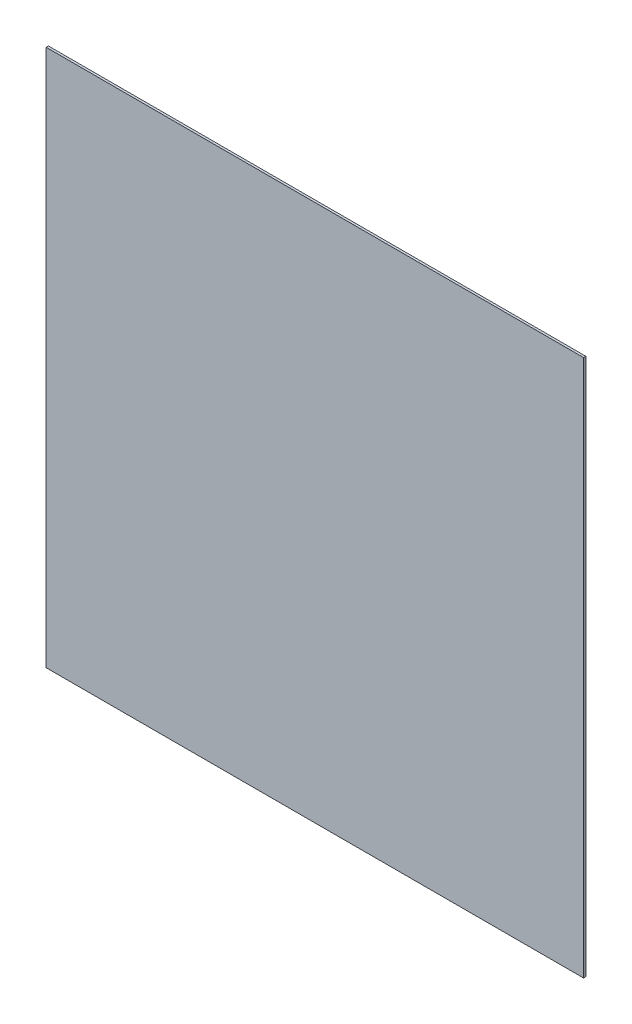
SolidWorks part; units mm, degrees
material "Mahogany"
ref_plane "Front Plane" through (0, 0, 0) normal (0, 0, 1) x (1, 0, 0)
ref_plane "Top Plane" through (0, 0, 0) normal (0, 1, 0) x (1, 0, 0)
ref_plane "Right Plane" through (0, 0, 0) normal (1, 0, 0) x (0, 0, -1)
sketch "Sketch1" plane through (0, 0, 0) normal (0, 0, 1) x (1, 0, 0)
  line L1 (-375, 375) -> (375, 375)
  line L2 (-375, 375) -> (-375, -375)
  line L3 (-375, -375) -> (375, -375)
  line L4 (375, 375) -> (375, -375)
  line L5 (-375, 375) -> (375, -375) construction
  line L6 (-375, -375) -> (375, 375) construction
  point P0 (0, 0)
  dimension "D1" = 750
  dimension "D2" = 750
extrude "Boss-Extrude1" add sketch "Sketch1" along normal blind 3.175
equation "\"W\"= 1750"
equation "\"L\"= 780"
equation "\"H\"= 780"
equation "\"ARM_BOLT_SPACING\"= 166"
equation "\"ARM_TO_WALL\"= 200"
equation "\"D1@Sketch1\"=\"L\"-30"
equation "\"D2@Sketch1\"=\"H\"-30"
